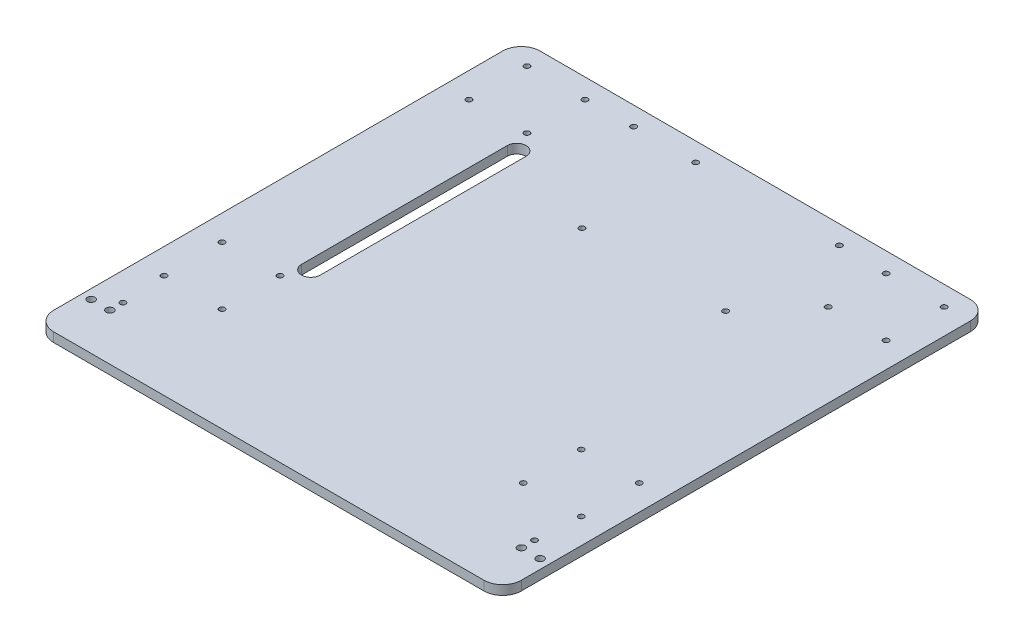
SolidWorks part; units mm, degrees
ref_plane "前视基准面" through (0, 0, 0) normal (0, 0, 1) x (1, 0, 0)
ref_plane "上视基准面" through (0, 0, 0) normal (0, 1, 0) x (1, 0, 0)
ref_plane "右视基准面" through (0, 0, 0) normal (1, 0, 0) x (0, 0, -1)
sketch "草图1" plane through (0, 0, 0) normal (0, 1, 0) x (1, 0, 0)
  line L0 (-125, 83) -> (-75, 83) construction
  line L1 (-125, -130) -> (125, -130)
  line L2 (-125, -130) -> (-125, 130)
  line L3 (-125, 130) -> (125, 130)
  line L4 (125, -130) -> (125, 130)
  line L5 (-125, -130) -> (125, 130) construction
  line L6 (-125, 130) -> (125, -130) construction
  line L7 (-125, -80) -> (-75, -80) construction
  line L8 (-125, -80) -> (-125, -38) construction
  line L9 (-125, -38) -> (-75, -38) construction
  line L10 (-75, -80) -> (-75, -38) construction
  line L11 (-117, -80) -> (-75, -80) construction
  line L12 (-117, -80) -> (-117, -38) construction
  line L13 (-117, -38) -> (-75, -38) construction
  line L14 (-75, -80) -> (-75, -38) construction
  line L15 (-117, -80) -> (-75, -38) construction
  line L16 (-117, -38) -> (-75, -80) construction
  line L17 (-111.5, -43.5) -> (-80.5, -43.5) construction
  line L18 (-111.5, -43.5) -> (-111.5, -74.5) construction
  line L19 (-111.5, -74.5) -> (-80.5, -74.5) construction
  line L20 (-80.5, -43.5) -> (-80.5, -74.5) construction
  line L21 (-125, 83) -> (-125, 125) construction
  line L22 (-125, 125) -> (-75, 125) construction
  line L23 (-75, 83) -> (-75, 125) construction
  line L24 (-117, 83) -> (-75, 83) construction
  line L25 (-117, 83) -> (-117, 125) construction
  line L26 (-117, 125) -> (-75, 125) construction
  line L27 (-75, 83) -> (-75, 125) construction
  line L28 (-117, 83) -> (-75, 125) construction
  line L29 (-117, 125) -> (-75, 83) construction
  line L30 (-111.5, 119.5) -> (-80.5, 119.5) construction
  line L31 (-111.5, 119.5) -> (-111.5, 88.5) construction
  line L32 (-111.5, 88.5) -> (-80.5, 88.5) construction
  line L33 (-80.5, 119.5) -> (-80.5, 88.5) construction
  line L34 (0, -130) -> (0, 130) construction
  line L35 (80.5, -43.5) -> (80.5, -74.5) construction
  line L36 (111.5, -74.5) -> (80.5, -74.5) construction
  line L37 (111.5, -43.5) -> (111.5, -74.5) construction
  line L38 (111.5, -43.5) -> (80.5, -43.5) construction
  line L39 (117, -38) -> (75, -80) construction
  line L40 (117, -80) -> (75, -38) construction
  line L41 (75, -80) -> (75, -38) construction
  line L42 (117, -38) -> (75, -38) construction
  line L43 (117, -80) -> (117, -38) construction
  line L44 (117, -80) -> (75, -80) construction
  line L45 (75, -80) -> (75, -38) construction
  line L46 (125, -38) -> (75, -38) construction
  line L47 (125, -80) -> (125, -38) construction
  line L48 (125, -80) -> (75, -80) construction
  line L49 (80.5, 119.5) -> (80.5, 88.5) construction
  line L50 (111.5, 88.5) -> (80.5, 88.5) construction
  line L51 (111.5, 119.5) -> (111.5, 88.5) construction
  line L52 (111.5, 119.5) -> (80.5, 119.5) construction
  line L53 (117, 125) -> (75, 83) construction
  line L54 (117, 83) -> (75, 125) construction
  line L55 (75, 83) -> (75, 125) construction
  line L56 (117, 125) -> (75, 125) construction
  line L57 (117, 83) -> (117, 125) construction
  line L58 (117, 83) -> (75, 83) construction
  line L59 (75, 83) -> (75, 125) construction
  line L60 (125, 125) -> (75, 125) construction
  line L61 (125, 83) -> (125, 125) construction
  line L62 (125, 83) -> (75, 83) construction
  line L63 (-75, 77.5) -> (-75, -32.5) construction
  line L64 (-70, 77.5) -> (-70, -32.5)
  line L65 (-80, 77.5) -> (-80, -32.5)
  line L67 (55, 120) -> (-21.8, 120) construction
  line L68 (55, 120) -> (55, 59.2) construction
  line L69 (55, 59.2) -> (-21.8, 59.2) construction
  line L70 (-21.8, 120) -> (-21.8, 59.2) construction
  circle A0 centre (-111.5, 119.5) radius 1.5
  circle A1 centre (-80.5, 119.5) radius 1.5
  circle A2 centre (-80.5, 88.5) radius 1.5
  circle A3 centre (-111.5, 88.5) radius 1.5
  circle A4 centre (-111.5, -43.5) radius 1.5
  circle A5 centre (-80.5, -43.5) radius 1.5
  circle A6 centre (-80.5, -74.5) radius 1.5
  circle A7 centre (-111.5, -74.5) radius 1.5
  circle A8 centre (111.5, -74.5) radius 1.5
  circle A9 centre (80.5, -74.5) radius 1.5
  circle A10 centre (80.5, -43.5) radius 1.5
  circle A11 centre (111.5, -43.5) radius 1.5
  circle A12 centre (111.5, 88.5) radius 1.5
  circle A13 centre (80.5, 88.5) radius 1.5
  circle A14 centre (80.5, 119.5) radius 1.5
  circle A15 centre (111.5, 119.5) radius 1.5
  circle A16 centre (-120, -105) radius 2
  circle A17 centre (-110, -105) radius 2
  circle A18 centre (110, -105) radius 2
  circle A19 centre (120, -105) radius 2
  circle A20 centre (-55, 120) radius 1.5
  circle A21 centre (55, 120) radius 1.5
  arc A22 (-70, 77.5) -> (-80, 77.5) centre (-75, 77.5) ccw
  circle A23 centre (-110, -98) radius 1.5
  arc A24 (-80, -32.5) -> (-70, -32.5) centre (-75, -32.5) ccw
  circle A25 centre (110, -98) radius 1.5
  circle A26 centre (55, 59.2) radius 1.5
  circle A27 centre (-21.8, 59.2) radius 1.5
  circle A28 centre (-21.8, 120) radius 1.5
  point P0 (0, 0)
  point P10 (-96, -59)
  point P22 (-96, 104)
  point P38 (-96, 104)
  point P45 (-96, -59)
  point P58 (96, -59)
  point P73 (96, 104)
  point P89 (-75, 22.5)
  dimension "D14" = 3
  dimension "D15" = 3
  dimension "D9" = 10
  dimension "D17" = 4
  dimension "D18" = 4
  dimension "D22" = 10
  dimension "D23" = 3
  dimension "D21" = 55
  dimension "D24" = 3
  dimension "D25" = 15
  dimension "D26" = 18
  dimension "D28" = 5
  dimension "D33" = 3
  dimension "D34" = 3
  dimension "D35" = 3
  dimension "D1" = 250
  dimension "D2" = 260
  dimension "D3" = 50
  dimension "D4" = 5
  dimension "D5" = 42
  dimension "D6" = 31
  dimension "D7" = 50
  dimension "D8" = 42
  dimension "D10" = 31
  dimension "D11" = 50
  dimension "D12" = 5
  dimension "D19" = 25
  dimension "D20" = 25
  dimension "D27" = 50
  dimension "D29" = 110
  dimension "D30" = 52.5
  dimension "D31" = 76.8
  dimension "D32" = 60.8
  dimension "D13" = 4
  dimension "D16" = 4
extrude "凸台-拉伸1" add sketch "草图1" along normal blind 5
fillet "圆角2" radius 10 4 edges at (125, 2.5, -130) (125, 2.5, 130) (-125, 2.5, -130) (-125, 2.5, 130)
